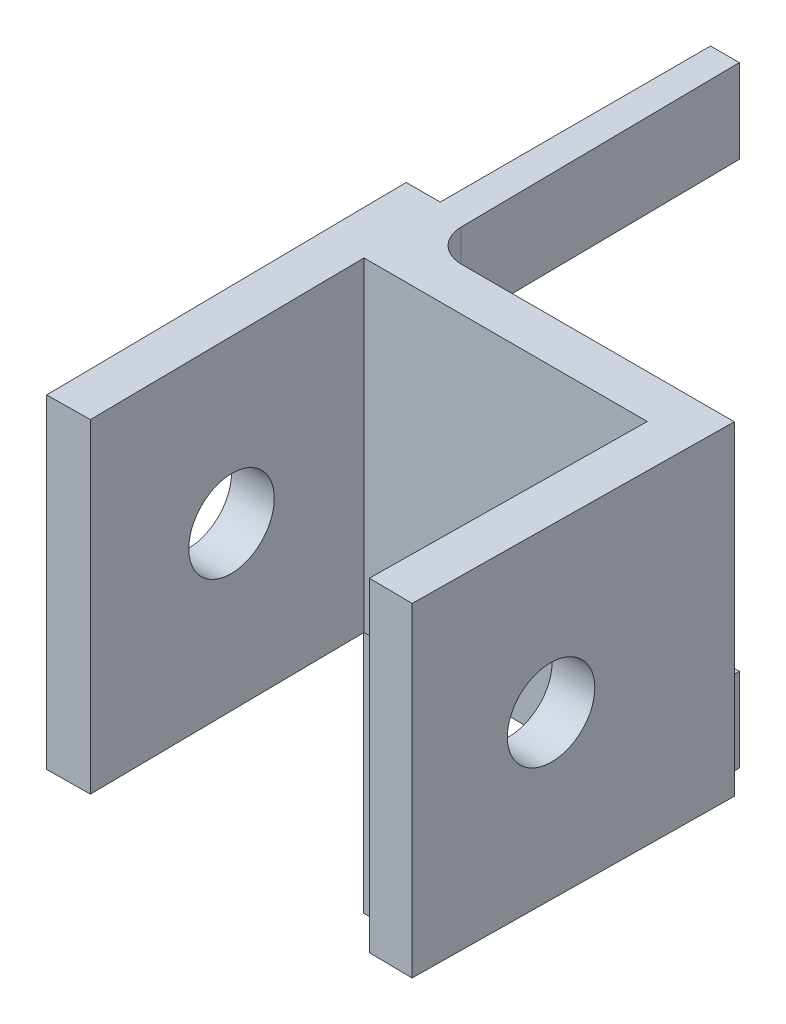
SolidWorks part; units mm, degrees
ref_plane "Front Plane" through (0, 0, 0) normal (0, 0, 1) x (1, 0, 0)
ref_plane "Top Plane" through (0, 0, 0) normal (0, 1, 0) x (1, 0, 0)
ref_plane "Right Plane" through (0, 0, 0) normal (1, 0, 0) x (0, 0, -1)
sketch "Sketch1" plane through (0, 0, 0) normal (0, 1, 0) x (1, 0, 0)
  line L0 (-12.8, -12.8) -> (-13.1, 12.8)
  line L1 (-12.8, 12.8) -> (12.8, 12.8) construction
  line L2 (-12.8, 12.8) -> (-12.8, -12.8) construction
  line L4 (12.8, 12.8) -> (12.8, -12.6) construction
  line L5 (-13.1, 12.8) -> (13.1, 12.8)
  line L6 (13.1, 12.8) -> (12.8, -12.6)
  line L7 (-16.7997, -12.8469) -> (-17.1471, 16.8)
  line L8 (-17.1471, 16.8) -> (17.1475, 16.8)
  line L9 (17.1475, 16.8) -> (16.7997, -12.6472)
  line L11 (-16.7997, -12.8469) -> (-12.8, -12.8)
  line L12 (12.8, -12.6) -> (16.7997, -12.6472)
  dimension "D1" = 25.6
  dimension "D2" = 25.4
  dimension "D3" = 0.3
  dimension "D4" = 0.3
  dimension "D5" = 4
extrude "Boss-Extrude1" add sketch "Sketch1" along normal blind 30
sketch "Sketch2" plane through (0, 30, 0) normal (0, 1, 0) x (1, 0, 0)
  line L0 (0.0002, 16.8) -> (0.0002, 30.8112) construction
  line L1 (17.1475, 16.8) -> (-17.1471, 16.8) construction
  line L2 (0.0002, 36.8) -> (-4.0998, 36.8) construction
  line L3 (0.0002, 36.8) -> (2.1002, 36.8) construction
  line L4 (-4.0998, 36.8) -> (-4.0998, 23.7851)
  line L5 (-2.0998, 36.8) -> (-2.0998, 23.7851)
  line L6 (-11.0849, 16.8) -> (-5.4334, 16.8)
  line L7 (-4.0998, 36.8) -> (-2.0998, 36.8)
  line L8 (4.1002, 36.8) -> (2.1002, 36.8)
  line L9 (11.0853, 16.8) -> (5.4337, 16.8)
  line L10 (2.1002, 36.8) -> (2.1002, 23.7851)
  line L11 (4.1002, 36.8) -> (4.1002, 23.7851)
  arc A0 (-4.0998, 23.7851) -> (-11.0849, 16.8) centre (-11.0849, 23.7851) cw
  arc A1 (-2.0998, 23.7851) -> (-5.4334, 16.8) centre (-11.0849, 23.7851) cw
  arc A2 (-2.0998, 23.7851) -> (-11.0849, 14.8) centre (-11.0849, 23.7851) cw construction
  arc A3 (4.1002, 23.7851) -> (11.0853, 16.8) centre (11.0853, 23.7851) ccw
  arc A4 (2.1002, 23.7851) -> (5.4337, 16.8) centre (11.0853, 23.7851) ccw
  dimension "D1" = 20
  dimension "D2" = 4.1
  dimension "D3" = 2
sketch "Sketch3" plane through (16.9467, 0, 0.2002) normal (0.9999, 0, 0.0118) x (0.0118, 0, -0.9999)
  line L0 (-12.448, 0) -> (12.952, 0) construction
  line L1 (0.252, 0) -> (0.252, 30) construction
  line L5 (-12.448, 30) -> (17.0013, 30) construction
  circle A0 centre (0.252, 15) radius 4
  dimension "D1" = 12.7
extrude "Cut-Extrude1" cut sketch "Sketch3" against normal blind 40
sketch "Sketch4" plane through (0, 0, -16.8) normal (0, 0, -1) x (-1, 0, 0)
  line L0 (17.1471, 0) -> (-17.1475, 30) construction
  line L1 (-0.0002, 15) -> (10.9998, 15) construction
  line L2 (10.9998, -5.5) -> (10.9998, 35.5)
  line L3 (10.9998, 35.5) -> (13.9998, 35.5)
  line L4 (10.9998, -5.5) -> (13.9998, -5.5)
  line L6 (13.9998, 35.5) -> (13.9998, -5.5)
  point P8 (10.9998, 15)
  dimension "D1" = 3
extrude "Boss-Extrude2" add sketch "Sketch4" against normal blind 4
sketch "Sketch5" plane through (0, 0, -16.8) normal (0, 0, -1) x (-1, 0, 0)
  line L1 (13.9998, 35.5) -> (13.9998, 43.25)
  line L11 (10.9998, 35.5) -> (10.9998, 43.25)
  line L17 (10.9998, 35.5) -> (13.9998, 35.5)
  line L18 (10.9998, 43.25) -> (13.9998, 43.25)
  line L21 (17.1471, 15) -> (-23.8791, 15) construction
  line L22 (17.1471, 30) -> (17.1471, 0) construction
  line L23 (10.9998, -13.25) -> (13.9998, -13.25)
  line L24 (10.9998, -5.5) -> (13.9998, -5.5)
  line L25 (10.9998, -5.5) -> (10.9998, -13.25)
  line L26 (13.9998, -5.5) -> (13.9998, -13.25)
extrude "Boss-Extrude3" add sketch "Sketch5" against normal blind 4 and the other way blind 25
sketch "Sketch6" plane through (-13.9998, 0, 0) normal (-1, 0, 0) x (0, 0, 1)
  line L0 (-16.8, 43.25) -> (-16.8, -13.25)
  line L1 (-41.8, 43.25) -> (-12.8, 43.25) construction
  line L2 (-12.8, -13.25) -> (-12.8, 43.25)
  line L3 (-12.8, -13.25) -> (-16.8, -13.25)
  line L4 (-12.8, 43.25) -> (-16.8, 43.25)
extrude "Boss-Extrude4" add sketch "Sketch6" along normal up to surface (3.1005 mm away) up to face at (-16.9087, 15, 3.5485)
sketch "Sketch7" plane through (-16.9479, 0, 0.1986) normal (-0.9999, 0, 0.0117) x (0.0117, 0, 0.9999)
  line L0 (12.6491, 30) -> (-40.2558, 30)
  line L1 (-40.2558, 30) -> (-53.5662, 38.8911)
  line L2 (-53.5662, 38.8911) -> (-52.1927, 50.0279)
  line L3 (-52.1927, 50.0279) -> (-13.8033, 48.7791)
  line L4 (-13.8033, 48.7791) -> (23.5061, 46.0536)
  line L5 (23.5061, 46.0536) -> (14.6716, 30)
  line L6 (14.6716, 30) -> (12.6491, 30)
  line L7 (12.6491, 0) -> (-49.961, 0)
  line L8 (-49.961, 0) -> (-43.2107, -24.3317)
  line L9 (-43.2107, -24.3317) -> (11.6534, -25.8063)
  line L10 (11.6534, -25.8063) -> (35.291, -15.9344)
  line L11 (35.291, -15.9344) -> (29.6892, -2.5212)
  line L12 (29.6892, -2.5212) -> (12.6491, 0)
extrude "Cut-Extrude2" cut sketch "Sketch7" against normal blind 62
sketch "Sketch9" plane through (0, 30, 0) normal (0, 1, 0) x (1, 0, 0)
  line L1 (-11.0459, 16.8) -> (-11.3857, 45.8)
  line L2 (-11.3857, 45.8) -> (-14.0467, 45.8)
  line L3 (-14.0467, 45.8) -> (-14.0467, 20.8)
  line L4 (-14.0467, 20.8) -> (-17.194, 20.8)
  line L5 (-17.194, 20.8) -> (-17.1471, 16.8)
  line L7 (-11.0467, 16.8) -> (-11.0459, 16.8)
  line L8 (-11.0467, 16.8) -> (-17.1471, 16.8)
extrude "Boss-Extrude6" add sketch "Sketch9" against normal blind 56.5
fillet "Fillet1" radius 3 1 edges at (-11.0459, 15, -16.8)
sketch "Sketch11" plane through (-10.8475, 0, 0.1271) normal (0.9999, 0, -0.0117) x (-0.0117, 0, -0.9999)
  line L0 (45.9303, 30) -> (45.9303, 22.25)
  line L1 (45.9303, -26.5) -> (45.9303, 30) construction
  line L2 (45.9303, 22.25) -> (20.9303, 22.25)
  line L3 (20.9303, 22.25) -> (20.9303, -18.75)
  line L4 (20.9303, -18.75) -> (57.6073, -18.75)
  line L6 (45.9303, 22.25) -> (60.0898, 19.7831)
  line L7 (60.0898, 19.7831) -> (57.6073, -18.75)
extrude "Cut-Extrude5" cut sketch "Sketch11" against normal blind 56.5
fillet "Fillet2" radius 3 1 edges at (-14.0965, 0, -16.8)
fillet "Fillet3" radius 3 1 edges at (-11.0456, 0, -16.7824)
